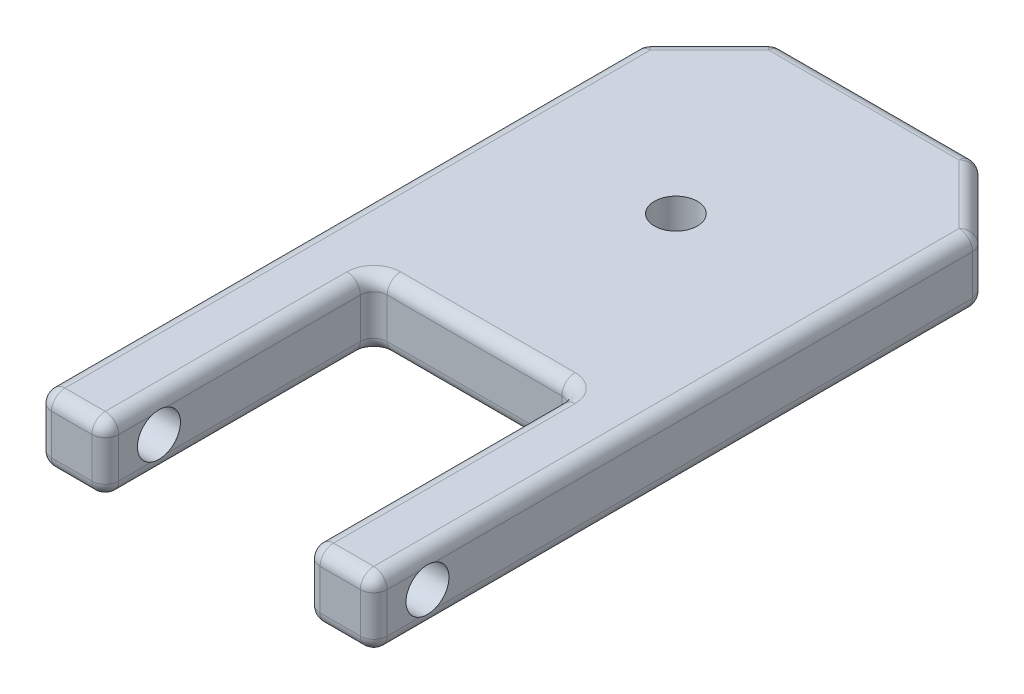
SolidWorks part; units mm, degrees
ref_plane "Front Plane" through (0, 0, 0) normal (0, 0, 1) x (1, 0, 0)
ref_plane "Top Plane" through (0, 0, 0) normal (0, 1, 0) x (1, 0, 0)
ref_plane "Right Plane" through (0, 0, 0) normal (1, 0, 0) x (0, 0, -1)
sketch "Sketch1" plane through (0, 0, 0) normal (0, 1, 0) x (1, 0, 0)
  line L1 (-12.5, -25) -> (12.5, -25)
  line L2 (-12.5, -25) -> (-12.5, 25)
  line L3 (-12.5, 25) -> (12.5, 25)
  line L4 (12.5, -25) -> (12.5, 25)
  line L5 (-12.5, -25) -> (12.5, 25) construction
  line L6 (-12.5, 25) -> (12.5, -25) construction
  point P0 (0, 0)
  dimension "D1" = 50
  dimension "D2" = 25
extrude "Boss-Extrude1" add sketch "Sketch1" along normal blind 5
sketch "Sketch3" plane through (0, 0, 25) normal (0, 0, 1) x (1, 0, 0)
  line L0 (-7.5, 5) -> (-7.5, 0)
  line L1 (-12.5, 5) -> (12.5, 5) construction
  line L2 (-12.5, 0) -> (12.5, 0) construction
  line L3 (-7.5, 0) -> (7.5, 0)
  line L4 (7.5, 0) -> (7.5, 5)
  line L5 (7.5, 5) -> (-7.5, 5)
  line L6 (-12.5, 5) -> (-12.5, 0) construction
  line L7 (12.5, 5) -> (12.5, 0) construction
  dimension "D1" = 5
  dimension "D2" = 5
extrude "Cut-Extrude1" cut sketch "Sketch3" against normal blind 20
sketch "Sketch5" plane through (12.5, 0, 0) normal (1, 0, 0) x (0, 0, -1)
  line L0 (-25, 5) -> (25, 5) construction
  line L3 (-25, 5) -> (-25, 0) construction
  circle A0 centre (-21, 2.5) radius 1.6
  dimension "D2" = 3.2
  dimension "D1" = 4
  dimension "D3" = 2.5
extrude "Cut-Extrude4" cut sketch "Sketch5" against normal blind 48.5
sketch "Sketch6" plane through (0, 5, 0) normal (0, 1, 0) x (1, 0, 0)
  line L0 (0, -5) -> (0, 25) construction
  line L1 (7.5, -5) -> (-7.5, -5) construction
  line L2 (12.5, 25) -> (-12.5, 25) construction
  circle A1 centre (0, 10) radius 1.6
  dimension "D2" = 3.2
  dimension "D3" = 0
  dimension "D6" = 15
extrude "Cut-Extrude5" cut sketch "Sketch6" against normal blind 48.5
sketch "Sketch7" plane through (0, 5, 0) normal (0, 1, 0) x (1, 0, 0)
  line L0 (-12.5, 25) -> (-12.5, -5)
  line L1 (-12.5, 25) -> (-12.5, -25) construction
  line L2 (-12.5, -5) -> (12.5, -5)
  line L3 (12.5, -25) -> (12.5, 25) construction
  line L4 (12.5, -5) -> (12.5, 25)
  line L5 (12.5, 25) -> (-12.5, 25)
chamfer "Chamfer1" distance 5 angle 45 2 edges at (-12.5, 2.5, -25) (12.5, 2.5, -25)
fillet "Fillet1" radius 1 30 edges at (12.5, 2.5, -20) (-10, 5, -22.5) (10, 5, -22.5) (-7.5, 2.5, -25) (7.5, 2.5, -25) (-10, 0, -22.5) (10, 0, -22.5) (-12.5, 2.5, -20) (-12.5, 2.5, 25) (12.5, 2.5, 25) (-10, 5, 25) (10, 5, 25) (-12.5, 5, 2.5) (0, 5, -25) (12.5, 5, 2.5) (-10, 0, 25) (10, 0, 25) (-12.5, 0, 2.5) (0, 0, -25) (12.5, 0, 2.5) (7.5, 5, 15) (7.5, 0, 15) (-7.5, 0, 15) (-7.5, 5, 15) (7.5, 2.5, 5) (0, 0, 5) (-7.5, 2.5, 5) (0, 5, 5) (7.5, 2.5, 25) (-7.5, 2.5, 25)
sketch "Sketch8" plane through (0, 0, 0) normal (0, -1, 0) x (1, 0, 0)
  line L0 (-12.5, 5) -> (12.5, 5)
  line L1 (12.5, 5) -> (12.5, -25)
  line L2 (-12.5, 5) -> (-12.5, -25)
  line L3 (-12.5, -25) -> (12.5, -25)
